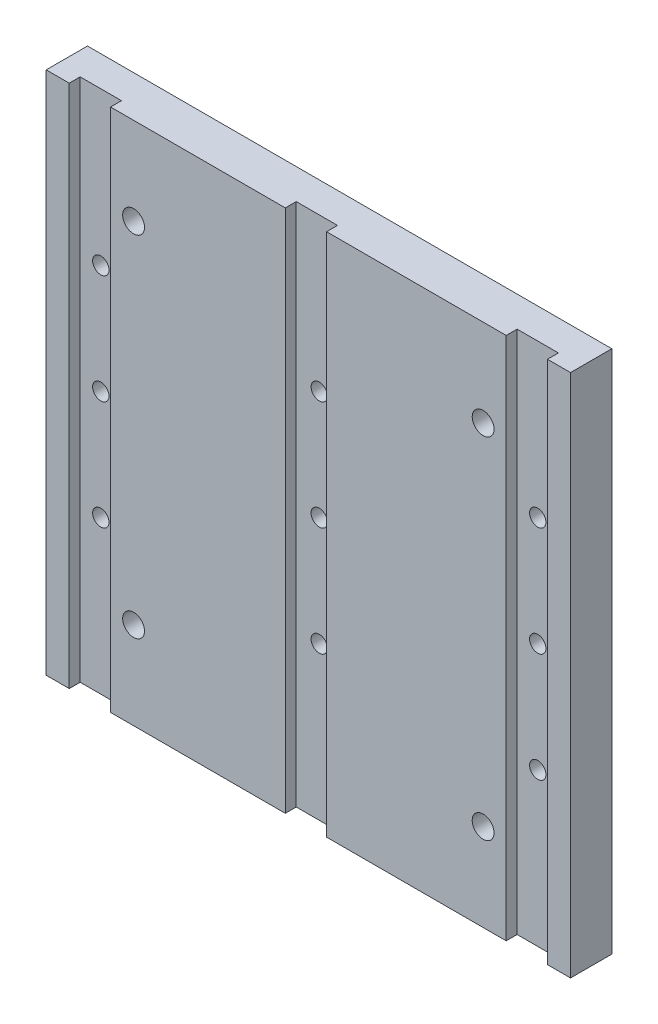
SolidWorks part; units mm, degrees
material "Acrylic (Medium-high impact)"
ref_plane "Front Plane" through (0, 0, 0) normal (0, 0, 1) x (1, 0, 0)
ref_plane "Top Plane" through (0, 0, 0) normal (0, 1, 0) x (1, 0, 0)
ref_plane "Right Plane" through (0, 0, 0) normal (1, 0, 0) x (0, 0, -1)
sketch "Sketch1" plane through (0, 0, 0) normal (0, 0, 1) x (1, 0, 0)
  line L1 (-76.2, 76.2) -> (76.2, 76.2)
  line L2 (-76.2, 76.2) -> (-76.2, -76.2)
  line L3 (-76.2, -76.2) -> (76.2, -76.2)
  line L4 (76.2, 76.2) -> (76.2, -76.2)
  line L5 (-76.2, 76.2) -> (76.2, -76.2) construction
  line L6 (-76.2, -76.2) -> (76.2, 76.2) construction
  circle A0 centre (-50.8, 50.8) radius 3.175
  circle A1 centre (50.8, 50.8) radius 3.175
  circle A2 centre (50.8, -50.8) radius 3.175
  circle A3 centre (-50.8, -50.8) radius 3.175
  point P0 (0, 0)
  dimension "D9" = 6.35
  dimension "D10" = 6.35
  dimension "D13" = 6.35
  dimension "D14" = 6.35
  dimension "D1" = 0
  dimension "D2" = 0
  dimension "D3" = 152.4
  dimension "D4" = 152.4
  dimension "D5" = 25.4
  dimension "D6" = 25.4
  dimension "D7" = 25.4
  dimension "D8" = 25.4
  dimension "D11" = 25.4
  dimension "D12" = 25.4
  dimension "D15" = 25.4
  dimension "D16" = 25.4
extrude "Boss-Extrude1" add sketch "Sketch1" along normal blind 12
sketch "Sketch2" plane through (0, 0, 12) normal (0, 0, 1) x (1, 0, 0)
  line L0 (-76.2, -76.2) -> (76.2, -76.2) construction
  line L1 (-69.5, 76.2) -> (-57.5, 76.2)
  line L2 (-69.5, 76.2) -> (-69.5, -76.2)
  line L3 (-69.5, -76.2) -> (-57.5, -76.2)
  line L4 (-57.5, 76.2) -> (-57.5, -76.2)
  line L5 (-69.5, 76.2) -> (-57.5, -76.2) construction
  line L6 (-69.5, -76.2) -> (-57.5, 76.2) construction
  line L7 (-6.7, 76.2) -> (5.3, 76.2)
  line L8 (-6.7, 76.2) -> (-6.7, -76.2)
  line L9 (-6.7, -76.2) -> (5.3, -76.2)
  line L10 (5.3, 76.2) -> (5.3, -76.2)
  line L11 (-6.7, 76.2) -> (5.3, -76.2) construction
  line L12 (-6.7, -76.2) -> (5.3, 76.2) construction
  line L13 (57.5, 76.2) -> (69.5, 76.2)
  line L14 (57.5, 76.2) -> (57.5, -76.2)
  line L15 (57.5, -76.2) -> (69.5, -76.2)
  line L16 (69.5, 76.2) -> (69.5, -76.2)
  line L17 (57.5, 76.2) -> (69.5, -76.2) construction
  line L18 (57.5, -76.2) -> (69.5, 76.2) construction
  line L19 (-76.2, 76.2) -> (-76.2, -76.2) construction
  line L20 (76.2, -76.2) -> (76.2, 76.2) construction
  point P0 (-63.5, 0)
  point P5 (-0.7, 0)
  point P10 (63.5, 0)
  dimension "D1" = 12
  dimension "D2" = 0
  dimension "D3" = 152.4
  dimension "D4" = 12.7
  dimension "D5" = 0
  dimension "D6" = 12
  dimension "D7" = 152.4
  dimension "D8" = 50.8
  dimension "D9" = 0
  dimension "D10" = 12
  dimension "D11" = 152.4
  dimension "D12" = 12.7
extrude "Cut-Extrude1" cut sketch "Sketch2" against normal blind 3.175
sketch "Sketch3" plane through (0, 0, 8.825) normal (0, 0, 1) x (1, 0, 0)
  line L0 (-63.5, 0) -> (-63.5, 31.75) construction
  line L1 (-63.5, 0) -> (-63.5, -31.75) construction
  line L2 (-69.5, 0) -> (-57.5, 0) construction
  line L3 (-69.5, 76.2) -> (-69.5, -76.2) construction
  line L4 (-57.5, -76.2) -> (-57.5, 76.2) construction
  line L5 (-67.4717, 76.2) -> (-67.4717, -76.2) construction
  line L6 (-57.5, 76.2) -> (-69.5, 76.2) construction
  line L7 (-69.5, -76.2) -> (-57.5, -76.2) construction
  circle A0 centre (-63.5, 0) radius 2.3812
  circle A1 centre (-63.5, 31.75) radius 2.3812
  circle A2 centre (-63.5, -31.75) radius 2.3812
  point P8 (0, 0)
  point P14 (-67.4717, 0)
  point P15 (0, 0)
  point P16 (-63.5, 0)
  dimension "D2" = 4.7625
  dimension "D1" = 31.75
extrude "Cut-Extrude2" cut sketch "Sketch3" against normal through all
sketch "Sketch4" plane through (0, 0, 0) normal (0, 0, -1) x (-1, 0, 0)
  circle A0 centre (63.5, 31.75) radius 3.9687
  circle A1 centre (63.5, 0) radius 3.9687
  circle A2 centre (63.5, -31.75) radius 3.9687
  dimension "D1" = 7.9375
extrude "Cut-Extrude3" cut sketch "Sketch4" against normal blind 2.54
pattern_linear "LPattern1" count 3 spacing 63.5 along (1, 0, 0) of "Cut-Extrude2", "Cut-Extrude3"
